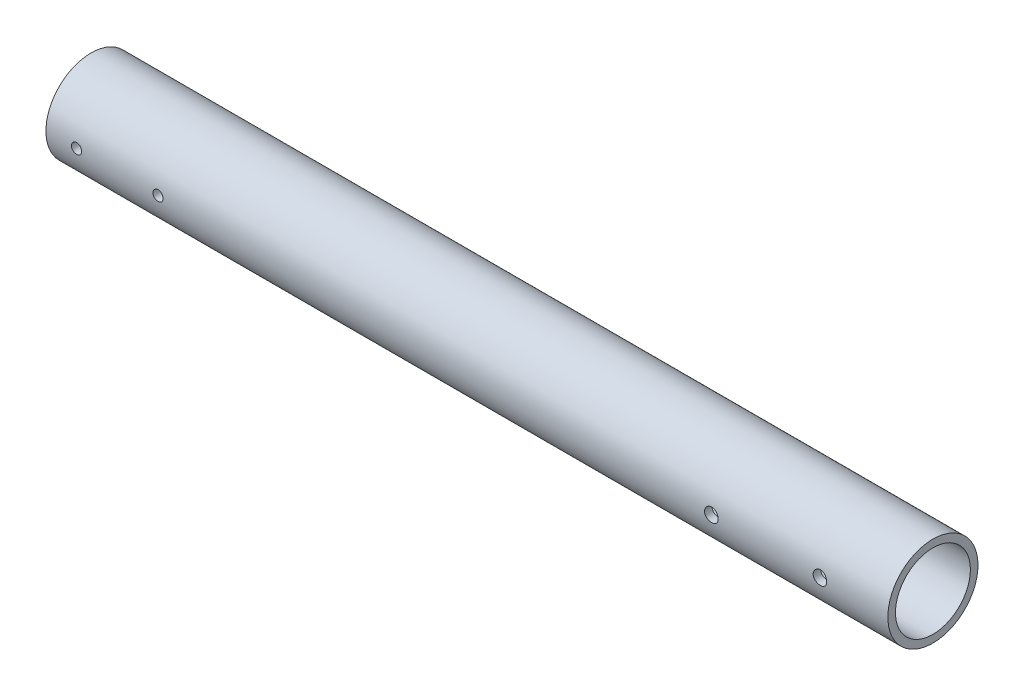
SolidWorks part; units mm, degrees
material "6061-T6 (SS)"
ref_plane "Front Plane" through (0, 0, 0) normal (0, 0, 1) x (1, 0, 0)
ref_plane "Top Plane" through (0, 0, 0) normal (0, 1, 0) x (1, 0, 0)
ref_plane "Right Plane" through (0, 0, 0) normal (1, 0, 0) x (0, 0, -1)
sketch "Sketch1" plane through (0, 0, 0) normal (1, 0, 0) x (0, 0, -1)
  circle A0 centre (0, 0) radius 21.082
  circle A1 centre (0, 0) radius 17.526
  dimension "D1" = 42.164
  dimension "D2" = 35.052
extrude "Boss-Extrude1" add sketch "Sketch1" along normal blind 196.85 and the other way blind 196.85
sketch "Sketch2" plane through (0, 0, 0) normal (0, 0, 1) x (1, 0, 0)
  line L0 (-196.85, 21.082) -> (-196.85, -21.082) construction
  circle A0 centre (-144.4625, 0) radius 2.3813
  circle A1 centre (-182.5625, 0) radius 2.3813
  dimension "D1" = 4.7625
  dimension "D2" = 14.2875
  dimension "D3" = 38.1
extrude "Cut-Extrude1" cut sketch "Sketch2" against normal through all both and the other way through all
sketch "Sketch3" plane through (0, 0, 0) normal (0, 0, 1) x (1, 0, 0)
  line L0 (196.85, -21.082) -> (196.85, 21.082) construction
  circle A0 centre (165.1, 0) radius 3.175
  circle A1 centre (114.3, 0) radius 3.175
  dimension "D1" = 6.35
  dimension "D2" = 6.35
  dimension "D3" = 31.75
  dimension "D4" = 50.8
extrude "Cut-Extrude2" cut sketch "Sketch3" along normal through all
